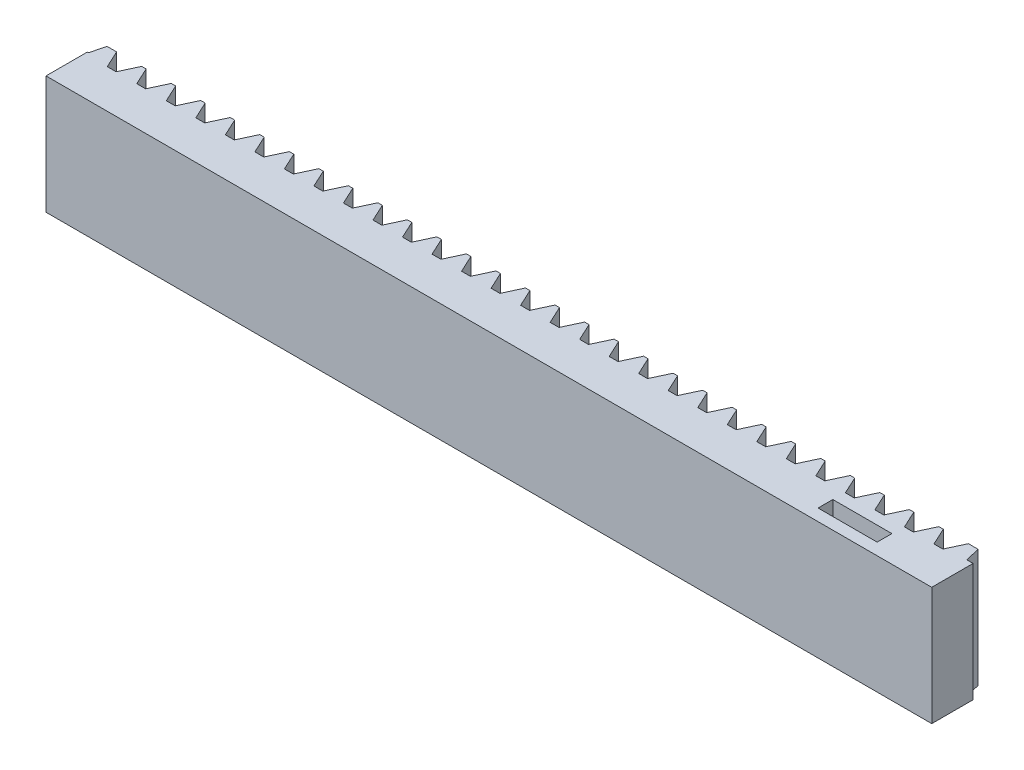
SolidWorks part; units mm, degrees
ref_plane "前基準面" through (0, 0, 0) normal (0, 0, 1) x (1, 0, 0)
ref_plane "上基準面" through (0, 0, 0) normal (0, 1, 0) x (1, 0, 0)
ref_plane "右基準面" through (0, 0, 0) normal (1, 0, 0) x (0, 0, -1)
sketch "草圖1" plane through (0, 0, 0) normal (0, 0, 1) x (1, 0, 0)
  line L1 (-12.9643, 5.0357) -> (47.0357, 5.0357)
  line L2 (-12.9643, 5.0357) -> (-12.9643, -4.9643)
  line L3 (-12.9643, -4.9643) -> (47.0357, -4.9643)
  line L4 (47.0357, 5.0357) -> (47.0357, -4.9643)
  dimension "D1" = 10
  dimension "D2" = 60
extrude "填料-伸長1" add sketch "草圖1" along normal blind 2.8
sketch "草圖3" plane through (0, 0, 0) normal (0, 1, 0) x (1, 0, 0)
  line L0 (-12.8816, 0) -> (-11.3816, 0)
  line L1 (-5.5, 0) -> (5.5, 0) construction
  line L2 (-12.1316, 0) -> (-12.1316, -0.4903) construction
  line L4 (-12.6316, 1) -> (-11.6316, 1)
  line L5 (-12.6316, 1) -> (-12.8816, 0)
  line L6 (-11.6316, 1) -> (-11.3816, 0)
  dimension "D1" = 1.5
  dimension "D2" = 1
  dimension "D3" = 0.5
  dimension "D4" = 1
extrude "填料-伸長2" add sketch "草圖3" along normal blind 5 and the other way blind 5
pattern_linear "直線複製排列1" count 30 spacing 2 along (1, 0, 0) of "填料-伸長2"
ref_plane "平面1" through (0, 5.0357, 0) normal (0, 1, 0) x (1, 0, 0)
sketch "草圖4" plane through (0, 5.0357, 0) normal (0, 1, 0) x (1, 0, 0)
  line L0 (-11.1316, 0.9852) -> (-11.1316, 0) construction
  line L1 (-11.5166, 0) -> (-11.4318, -0.1825)
  line L3 (-11.6316, 1) -> (-12.6316, 1) construction
  line L4 (-11.9816, 1) -> (-11.5166, 0)
  line L5 (-55, 0) -> (55, 0) construction
  line L6 (-10.2816, 1) -> (-11.9816, 1)
  line L8 (-10.2816, 1) -> (-10.7465, 0)
  line L9 (-11.4318, -0.1825) -> (-10.8314, -0.1825)
  line L10 (-10.7465, 0) -> (-10.8314, -0.1825)
  line L11 (-11.1316, -0.1825) -> (-11.1316, -1.191) construction
  point P12 (-11.1316, 0)
  point P14 (-11.1316, 1)
  point P16 (-11.1316, -0.1825)
  dimension "D1" = 0.85
  dimension "D2" = 0.5
extrude "除料-伸長1" cut sketch "草圖4" against normal blind 10.1
pattern_linear "直線複製排列2" count 29 spacing 2 along (1, 0, 0) of "除料-伸長1"
sketch "草圖5" plane through (0, 0, 0) normal (0, 0, 1) x (1, 0, 0)
  line L0 (-12.9643, 0.0357) -> (47.0357, 0.0357) construction
  line L1 (-12.9643, 5.0357) -> (-12.9643, -4.9643) construction
  line L2 (47.0357, -4.9643) -> (47.0357, 5.0357) construction
  line L3 (-12.9643, -3.9643) -> (-12.9643, -4.9643)
  line L4 (-12.9643, -3.9643) -> (47.0357, -3.9643)
  line L7 (47.0357, 4.0357) -> (47.0357, 5.0357)
  line L9 (-12.9643, 4.0357) -> (-12.9643, 5.0357)
  line L10 (-12.9643, 4.0357) -> (47.0357, 4.0357)
  line L11 (-12.9643, 5.0357) -> (47.0357, 5.0357)
  line L12 (47.0357, -3.9643) -> (47.0357, -5.0888)
  line L13 (47.0357, -5.0888) -> (-12.9643, -5.414)
  line L14 (-12.9643, -5.414) -> (-12.9643, -4.9643)
  dimension "D1" = 1
extrude "除料-伸長4" cut sketch "草圖5" against normal blind 5 and the other way blind 5
ref_plane "平面2" through (0, 4.0357, 0) normal (0, 1, 0) x (1, 0, 0)
sketch "草圖6" plane through (0, 4.0357, 0) normal (0, 1, 0) x (1, 0, 0)
  line L0 (47.0357, -2.8) -> (47.0357, 0) construction
  line L1 (38.5357, -1) -> (42.5357, -1)
  line L2 (38.5357, -1) -> (38.5357, -2)
  line L3 (38.5357, -2) -> (42.5357, -2)
  line L4 (42.5357, -1) -> (42.5357, -2)
  line L5 (47.0357, -2.8) -> (-12.9643, -2.8) construction
  dimension "D1" = 4.5
  dimension "D2" = 4
  dimension "D3" = 1
  dimension "D4" = 0.8
extrude "除料-伸長5" cut sketch "草圖6" against normal blind 10 and the other way blind 10
